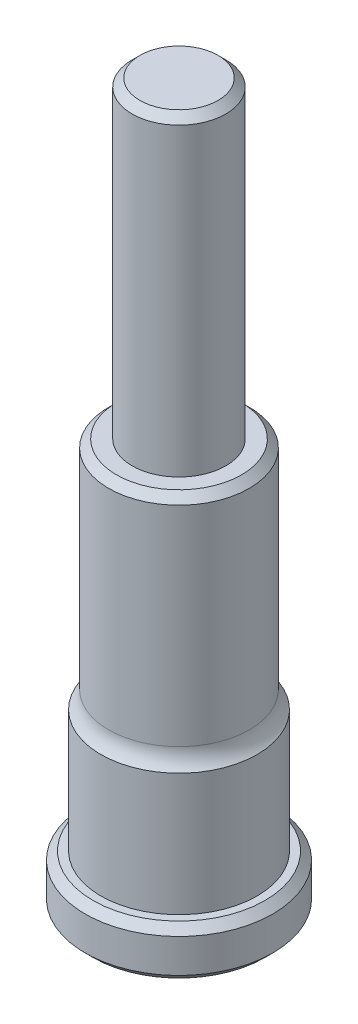
SolidWorks part; units mm, degrees
ref_plane "Front Plane" through (0, 0, 0) normal (0, 0, 1) x (1, 0, 0)
ref_plane "Top Plane" through (0, 0, 0) normal (0, 1, 0) x (1, 0, 0)
ref_plane "Right Plane" through (0, 0, 0) normal (1, 0, 0) x (0, 0, -1)
ref_axis "X" through (88.99, 0, 0) along (-1, 0, 0)
ref_axis "Y" through (0, 55, 0) along (0, -1, 0)
ref_axis "Z" through (0, 0, -88.99) along (0, 0, 1)
sketch "Sketch1" plane through (0, 0, 0) normal (0, 0, 1) x (1, 0, 0)
  line L0 (0, 0) -> (-61.4788, 0) construction
  line L1 (0, 0) -> (0, 92) construction
  line L2 (-5, 0) -> (-10, 0)
  line L3 (-10, 6.32) -> (-10, 22)
  line L4 (-10, 22) -> (-9, 22)
  line L5 (-6, 52) -> (-6, 92)
  line L6 (-6, 92) -> (0, 92)
  line L7 (0, 92) -> (0, 18)
  line L8 (0, 18) -> (-5, 18)
  line L9 (-5, 18) -> (-5, 0)
  line L10 (-9, 22) -> (-9, 52)
  line L11 (-9, 52) -> (-6, 52)
  line L13 (-10, 0) -> (-12, 0)
  line L15 (-10, 6.32) -> (-12, 6.32)
  line L16 (-12, 0) -> (-12, 6.32)
  dimension "D1" = 12
  dimension "D2" = 20
  dimension "D3" = 10
  dimension "D4" = 18
  dimension "D5" = 22
  dimension "D6" = 92
  dimension "D7" = 52
  dimension "D8" = 18
  dimension "D9" = 6.32
  dimension "D10" = 2
revolve "Revolve1" add sketch "Sketch1" angle 360 about L1
fillet "Fillet1" radius 3 1 edges at (9, 22, 0)
chamfer "Chamfer2" distance 1 angle 45 1 edges at (6, 92, 0)
chamfer "Chamfer3" distance 1 angle 45 1 edges at (9, 52, 0)
chamfer "Chamfer4" distance 1 angle 45 2 edges at (5, 0, 0) (12, 0, 0)
chamfer "Chamfer5" distance 1 angle 45 1 edges at (12, 6.32, 0)
